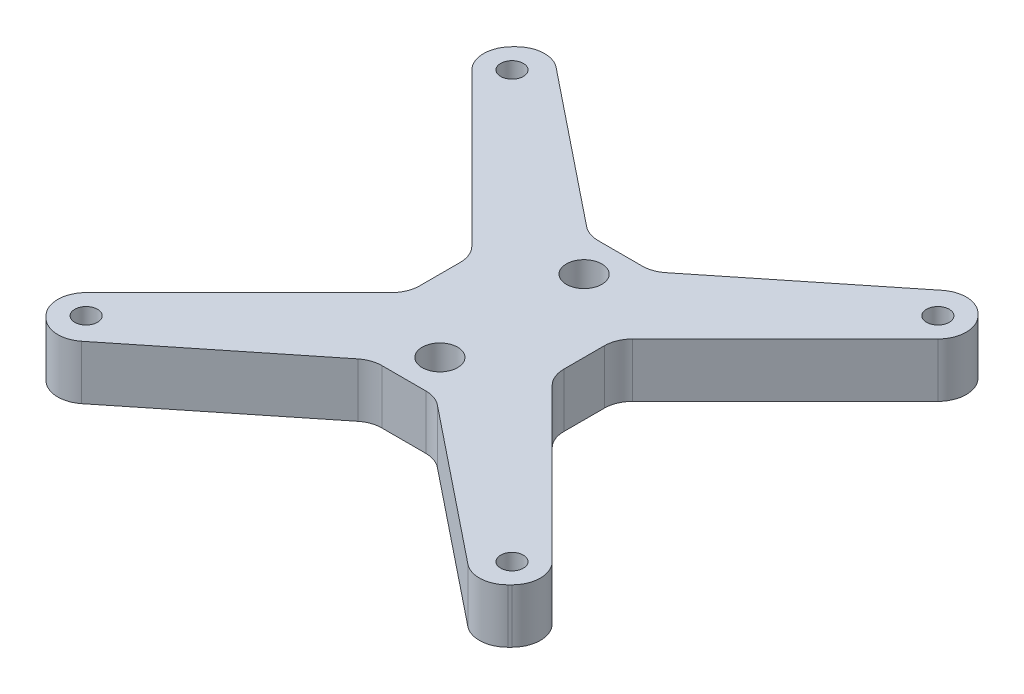
SolidWorks part; units mm, degrees
ref_plane "Front Plane" through (0, 0, 0) normal (0, 0, 1) x (1, 0, 0)
ref_plane "Top Plane" through (0, 0, 0) normal (0, 1, 0) x (1, 0, 0)
ref_plane "Right Plane" through (0, 0, 0) normal (1, 0, 0) x (0, 0, -1)
sketch "Sketch1" plane through (0, 0, 0) normal (0, 1, 0) x (1, 0, 0)
  line L4 (-37.5, -37.5) -> (37.5, 37.5) construction
  line L5 (37.5, -37.5) -> (-37.5, 37.5) construction
  line L6 (-37.5, 37.5) -> (37.5, 37.5) construction
  line L7 (-12.7, 5.6289) -> (-44.5711, 37.5)
  line L8 (-44.5711, 37.5) -> (-37.5, 44.5711)
  line L10 (-5.6289, 12.7) -> (5.6289, 12.7) construction
  line L11 (5.6289, 12.7) -> (37.5, 44.5711) construction
  line L12 (37.5, 44.5711) -> (44.5711, 37.5)
  line L13 (44.5711, 37.5) -> (12.7, 5.6289)
  line L14 (12.7, 5.6289) -> (12.7, -5.6289)
  line L15 (12.7, -5.6289) -> (44.5711, -37.5)
  line L16 (44.5711, -37.5) -> (37.5, -44.5711)
  line L17 (37.5, -44.5711) -> (5.6289, -12.7) construction
  line L18 (5.6289, -12.7) -> (-5.6289, -12.7) construction
  line L19 (-5.6289, -12.7) -> (-37.5, -44.5711) construction
  line L20 (-37.5, -44.5711) -> (-44.5711, -37.5)
  line L21 (-44.5711, -37.5) -> (-12.7, -5.6289)
  line L22 (-12.7, -5.6289) -> (-12.7, 5.6289)
  line L23 (0, 12.7) -> (0, -12.7) construction
  line L24 (-37.5, 44.5711) -> (-5.6289, 12.7) construction
  line L25 (37.5, 37.5) -> (41.0355, 41.0355) construction
  line L26 (37.5, -37.5) -> (41.0355, -41.0355) construction
  line L27 (-37.5, -37.5) -> (-41.0355, -41.0355) construction
  line L28 (-37.5, 37.5) -> (-41.0355, 41.0355) construction
  line L29 (-37.5, -37.5) -> (37.5, -37.5) construction
  line L30 (-5.6289, -12.7) -> (5.6289, -12.7) construction
  line L31 (-5.6289, -12.7) -> (-5.6289, -19.05) construction
  line L32 (5.6289, -12.7) -> (5.6289, -19.05) construction
  line L33 (-5.6289, -19.05) -> (5.6289, -19.05)
  line L34 (-5.6289, 12.7) -> (5.6289, 12.7) construction
  line L35 (-5.6289, 12.7) -> (-5.6289, 19.05) construction
  line L36 (5.6289, 12.7) -> (5.6289, 19.05) construction
  line L37 (-5.6289, 19.05) -> (5.6289, 19.05)
  line L38 (5.6289, 19.05) -> (37.5, 44.5711)
  line L39 (-37.5, 44.5711) -> (-5.6289, 19.05)
  line L40 (-37.5, -44.5711) -> (-5.6289, -19.05)
  line L41 (5.6289, -19.05) -> (37.5, -44.5711)
  circle A0 centre (37.5, 37.5) radius 2
  circle A1 centre (37.5, -37.5) radius 2
  circle A2 centre (-37.5, -37.5) radius 2
  circle A3 centre (-37.5, 37.5) radius 2
  circle A5 centre (0, 12.7) radius 3.125
  circle A6 centre (0, -12.7) radius 3.125
  point P1 (0, 0)
  point P28 (0, 0)
  dimension "D2" = 4
  dimension "D6" = 6.25
  dimension "D1" = 75
  dimension "D3" = 25.4
  dimension "D4" = 10
  dimension "D5" = 6.35
  dimension "5" = 5
  dimension "D9" = 25.4
extrude "Boss-Extrude1" add sketch "Sketch1" along normal blind 9.525
fillet "Fillet1" radius 5 16 edges at (12.7, 4.7625, -5.6289) (12.7, 4.7625, 5.6289) (44.5711, 4.7625, 37.5) (-44.5711, 4.7625, 37.5) (-12.7, 4.7625, 5.6289) (-44.5711, 4.7625, -37.5) (44.5711, 4.7625, -37.5) (-12.7, 4.7625, -5.6289) (5.6289, 4.7625, 19.05) (-5.6289, 4.7625, 19.05) (-37.5, 4.7625, 44.5711) (37.5, 4.7625, 44.5711) (37.5, 4.7625, -44.5711) (5.6289, 4.7625, -19.05) (-5.6289, 4.7625, -19.05) (-37.5, 4.7625, -44.5711)
